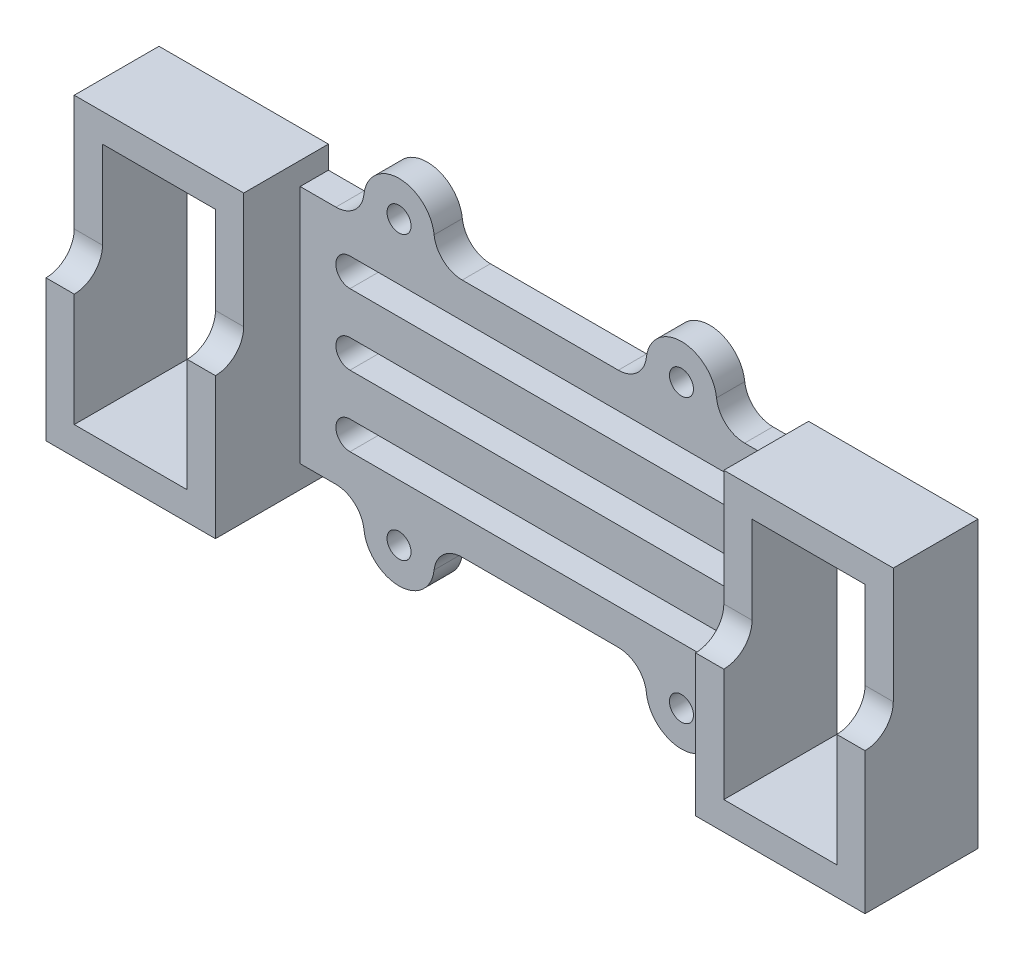
SolidWorks part; units mm, degrees
ref_plane "Front Plane" through (0, 0, 0) normal (0, 0, 1) x (1, 0, 0)
ref_plane "Top Plane" through (0, 0, 0) normal (0, 1, 0) x (1, 0, 0)
ref_plane "Right Plane" through (0, 0, 0) normal (1, 0, 0) x (0, 0, -1)
sketch "Sketch1" plane through (0, 0, 0) normal (0, 0, 1) x (1, 0, 0)
  line L0 (0, 0) -> (0, 50000) construction
  line L10 (0, 0) -> (50000, 0) construction
  line L14 (-4.2313, 8.65) -> (4.2313, 8.65)
  line L15 (8.65, 4.2313) -> (8.65, -4.2313)
  line L16 (-8.65, 4.2313) -> (-8.65, -4.2313)
  line L17 (-4.2313, -8.65) -> (4.2313, -8.65)
  circle A3 centre (10, 10) radius 1
  arc A4 (10.825, 7.1157) -> (7.1157, 10.825) centre (10, 10) ccw
  arc A5 (8.65, 4.2313) -> (10.825, 7.1157) centre (11.65, 4.2313) cw
  arc A6 (4.2313, 8.65) -> (7.1157, 10.825) centre (4.2313, 11.65) ccw
  arc A7 (-4.2313, 8.65) -> (-7.1157, 10.825) centre (-4.2313, 11.65) cw
  arc A8 (-8.65, 4.2313) -> (-10.825, 7.1157) centre (-11.65, 4.2313) ccw
  arc A9 (-10.825, 7.1157) -> (-7.1157, 10.825) centre (-10, 10) cw
  circle A10 centre (-10, 10) radius 1
  circle A11 centre (-10, -10) radius 1
  arc A12 (-10.825, -7.1157) -> (-7.1157, -10.825) centre (-10, -10) ccw
  arc A13 (-8.65, -4.2313) -> (-10.825, -7.1157) centre (-11.65, -4.2313) cw
  arc A14 (-4.2313, -8.65) -> (-7.1157, -10.825) centre (-4.2313, -11.65) ccw
  arc A15 (4.2313, -8.65) -> (7.1157, -10.825) centre (4.2313, -11.65) cw
  arc A16 (8.65, -4.2313) -> (10.825, -7.1157) centre (11.65, -4.2313) ccw
  arc A17 (10.825, -7.1157) -> (7.1157, -10.825) centre (10, -10) cw
  circle A18 centre (10, -10) radius 1
  point P7 (0, -8.65)
  point P24 (8.65, 0)
  point P25 (0, 8.65)
  point P41 (-8.65, 0)
  dimension "D1" = 8.65
  dimension "D5" = 2
  dimension "D6" = 6
  dimension "D7" = 3
  dimension "D2" = 8.65
  dimension "D3" = 10
  dimension "D4" = 10
sketch "Sketch2" plane through (0, 0, 0) normal (0, 0, 1) x (1, 0, 0)
  line L4 (-200000, 0) -> (250000, 0) construction
  line L5 (0, -200000) -> (0, 250000) construction
  line L6 (5.5279, 8.5) -> (-5.5279, 8.5)
  line L8 (0, 0) -> (0, 50000) construction
  line L11 (17, 8.5) -> (14.4721, 8.5)
  line L12 (0, 0) -> (47513.2931, 0) construction
  line L13 (17, 8.5) -> (17, 10.1)
  line L14 (17, 10.1) -> (29, 10.1)
  line L15 (29, 10.1) -> (29, 0)
  line L21 (19, -8.1) -> (19, 8.1)
  line L22 (19, 8.1) -> (27, 8.1)
  line L23 (27, -8.1) -> (27, 8.1)
  line L24 (0, 0) -> (-47513.2931, 0) construction
  line L25 (-27, -8.1) -> (-27, 8.1)
  line L26 (-19, 8.1) -> (-27, 8.1)
  line L27 (-19, -8.1) -> (-19, 8.1)
  line L28 (-29, 10.1) -> (-29, 0)
  line L29 (-17, 10.1) -> (-29, 10.1)
  line L30 (-17, 8.5) -> (-17, 10.1)
  line L31 (-17, 8.5) -> (-14.4721, 8.5)
  line L32 (-17, -8.5) -> (-14.4721, -8.5)
  line L33 (-17, -8.5) -> (-17, -10.1)
  line L34 (-17, -10.1) -> (-29, -10.1)
  line L35 (-29, -10.1) -> (-29, 0)
  line L36 (-19, -8.1) -> (-27, -8.1)
  line L37 (19, -8.1) -> (27, -8.1)
  line L38 (29, -10.1) -> (29, 0)
  line L39 (17, -10.1) -> (29, -10.1)
  line L40 (17, -8.5) -> (17, -10.1)
  line L41 (17, -8.5) -> (14.4721, -8.5)
  line L42 (5.5279, -8.5) -> (-5.5279, -8.5)
  line L46 (-13.4721, 5) -> (13.4721, 5) construction
  line L47 (-13.4721, 6) -> (13.4721, 6)
  line L48 (-13.4721, 4) -> (13.4721, 4)
  line L49 (13.4721, 0) -> (-13.4721, 0) construction
  line L50 (13.4721, -1) -> (-13.4721, -1)
  line L51 (13.4721, 1) -> (-13.4721, 1)
  line L52 (13.4721, -5) -> (-13.4721, -5) construction
  line L53 (13.4721, -6) -> (-13.4721, -6)
  line L54 (13.4721, -4) -> (-13.4721, -4)
  arc A0 (12.4845, 10.2778) -> (7.5155, 10.2778) centre (10, 10) ccw
  circle A1 centre (10, 10) radius 0.85
  arc A2 (-14.4721, 8.5) -> (-12.4845, 10.2778) centre (-14.4721, 10.5) ccw
  arc A3 (5.5279, 8.5) -> (7.5155, 10.2778) centre (5.5279, 10.5) ccw
  arc A4 (14.4721, 8.5) -> (12.4845, 10.2778) centre (14.4721, 10.5) cw
  arc A5 (-5.5279, 8.5) -> (-7.5155, 10.2778) centre (-5.5279, 10.5) cw
  circle A6 centre (-10, 10) radius 0.85
  arc A7 (-12.4845, 10.2778) -> (-7.5155, 10.2778) centre (-10, 10) cw
  arc A8 (-12.4845, -10.2778) -> (-7.5155, -10.2778) centre (-10, -10) ccw
  circle A9 centre (-10, -10) radius 0.85
  arc A10 (-5.5279, -8.5) -> (-7.5155, -10.2778) centre (-5.5279, -10.5) ccw
  arc A11 (14.4721, -8.5) -> (12.4845, -10.2778) centre (14.4721, -10.5) ccw
  arc A12 (5.5279, -8.5) -> (7.5155, -10.2778) centre (5.5279, -10.5) cw
  arc A13 (-14.4721, -8.5) -> (-12.4845, -10.2778) centre (-14.4721, -10.5) cw
  circle A14 centre (10, -10) radius 0.85
  arc A15 (12.4845, -10.2778) -> (7.5155, -10.2778) centre (10, -10) cw
  arc A16 (-13.4721, 6) -> (-13.4721, 4) centre (-13.4721, 5) ccw
  arc A17 (13.4721, 4) -> (13.4721, 6) centre (13.4721, 5) ccw
  arc A18 (13.4721, -1) -> (13.4721, 1) centre (13.4721, 0) ccw
  arc A19 (-13.4721, 1) -> (-13.4721, -1) centre (-13.4721, 0) ccw
  arc A20 (13.4721, -6) -> (13.4721, -4) centre (13.4721, -5) ccw
  arc A21 (-13.4721, -4) -> (-13.4721, -6) centre (-13.4721, -5) ccw
  point P5 (0, 0)
  point P16 (17, 9.3)
  point P27 (29, 0)
  point P48 (0, 8.5)
  point P67 (0, 0)
  point P69 (-19, 0)
  point P70 (-27, 0)
  point P71 (27, 0)
  point P72 (19, 0)
  point P76 (0, -8.5)
  point P79 (0, 5)
  point P84 (0, 0)
  point P91 (0, -5)
  point P98 (-29, 0)
  dimension "D1" = 8.5
  dimension "D5" = 5
  dimension "D6" = 1.7
  dimension "D7" = 2
  dimension "D12" = 1
  dimension "D13" = 1
  dimension "D2" = 17
  dimension "D3" = 2
  dimension "D4" = 2
  dimension "D9" = 2
  dimension "D10" = 8
  dimension "D11" = 8.1
  dimension "D14" = 5
  dimension "D15" = 5
extrude "Boss-Extrude1" add sketch "Sketch2" along normal blind 2
sketch "Sketch6" plane through (0, 0, 2) normal (0, 0, 1) x (1, 0, 0)
  line L1 (-27, 8.1) -> (-19, 8.1)
  line L2 (-27, 8.1) -> (-27, -8.1)
  line L3 (-27, -8.1) -> (-19, -8.1)
  line L4 (-19, 8.1) -> (-19, -8.1)
  line L5 (-29, 10.1) -> (-17, 10.1)
  line L6 (-29, 10.1) -> (-29, -10.1)
  line L7 (-29, -10.1) -> (-17, -10.1)
  line L8 (-17, 10.1) -> (-17, -10.1)
  line L9 (17, 10.1) -> (29, 10.1)
  line L10 (17, 10.1) -> (17, -10.1)
  line L11 (17, -10.1) -> (29, -10.1)
  line L12 (29, 10.1) -> (29, -10.1)
  line L13 (27, -8.1) -> (19, -8.1)
  line L14 (27, -8.1) -> (27, 8.1)
  line L15 (27, 8.1) -> (19, 8.1)
  line L16 (19, -8.1) -> (19, 8.1)
extrude "Boss-Extrude5" add sketch "Sketch6" along normal blind 4
sketch "Sketch7" plane through (0, 0, 6) normal (0, 0, 1) x (1, 0, 0)
  line L12 (17, -0.1) -> (19, -0.1)
  line L13 (17, 10.1) -> (17, -10.1) construction
  line L14 (19, 8.1) -> (19, -8.1) construction
  line L15 (19, -0.1) -> (19, -8.1)
  line L16 (19, -8.1) -> (27, -8.1) construction
  line L17 (19, -8.1) -> (27, -8.1)
  line L18 (27, -8.1) -> (27, -0.1)
  line L19 (27, -8.1) -> (27, 8.1) construction
  line L20 (27, -0.1) -> (29, -0.1)
  line L21 (29, -10.1) -> (29, 10.1) construction
  line L22 (29, -0.1) -> (29, -10.1)
  line L23 (29, -10.1) -> (17, -10.1)
  line L24 (17, -10.1) -> (17, -0.1)
  line L25 (0, -3.3) -> (0, 3.3) construction
  line L26 (-17, -10.1) -> (-17, -0.1)
  line L27 (-29, -10.1) -> (-17, -10.1)
  line L28 (-29, -0.1) -> (-29, -10.1)
  line L29 (-27, -0.1) -> (-29, -0.1)
  line L30 (-27, -8.1) -> (-27, -0.1)
  line L31 (-19, -8.1) -> (-27, -8.1)
  line L32 (-19, -0.1) -> (-19, -8.1)
  line L33 (-17, -0.1) -> (-19, -0.1)
  point P0 (29, 4.0093)
  dimension "D1" = 8
extrude "Boss-Extrude6" add sketch "Sketch7" along normal blind 2
fillet "Fillet1" radius 2 4 edges at (28, -0.1, 6) (18, -0.1, 6) (-18, -0.1, 6) (-28, -0.1, 6)
